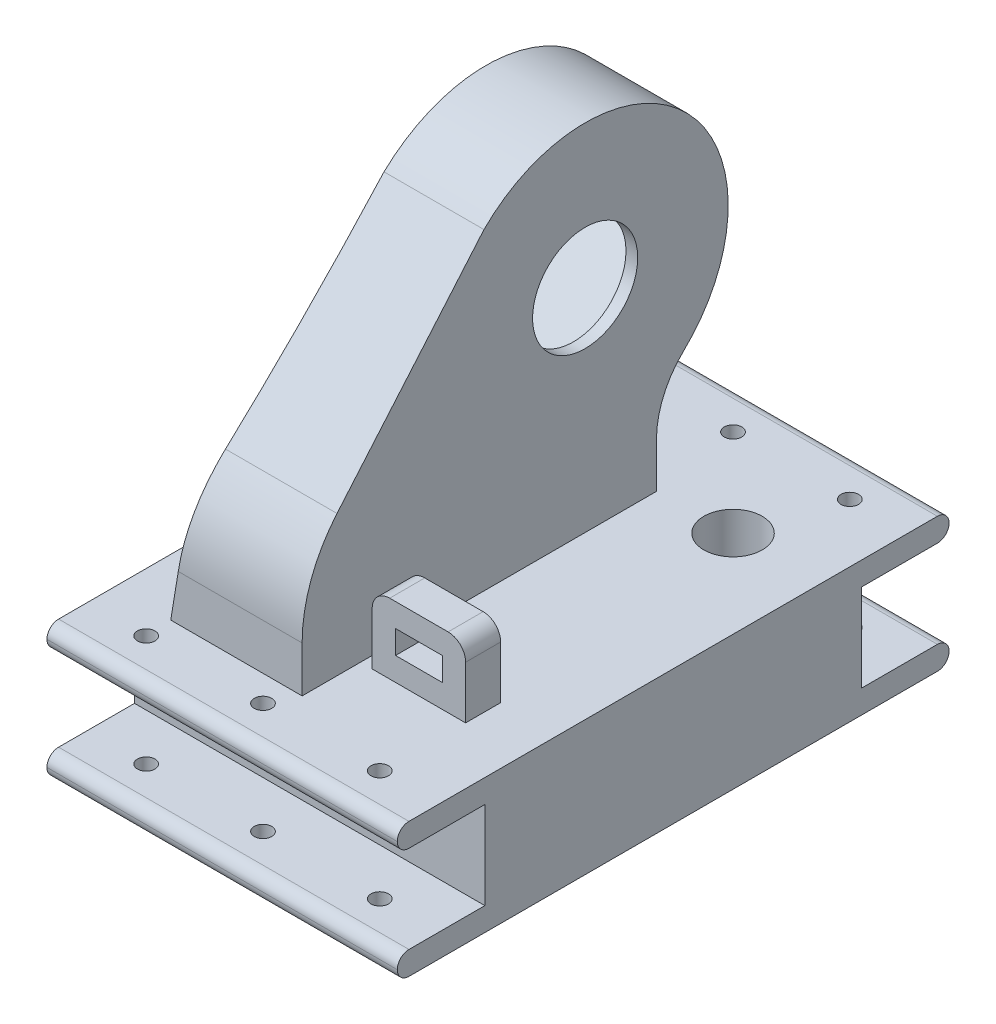
SolidWorks part; units mm, degrees
ref_plane "Front Plane" through (0, 0, 0) normal (0, 0, 1) x (1, 0, 0)
ref_plane "Top Plane" through (0, 0, 0) normal (0, 1, 0) x (1, 0, 0)
ref_plane "Right Plane" through (0, 0, 0) normal (1, 0, 0) x (0, 0, -1)
sketch "Sketch2" plane through (0, 0, 0) normal (0, 1, 0) x (1, 0, 0)
  circle A0 centre (0, 0) radius 48.5
  dimension "D1" = 97
extrude "Boss-Extrude1" add sketch "Sketch2" along normal blind 4
ref_plane "Plane1" through (-4, 0, 0) normal (1, 0, 0) x (0, 0, -1)
sketch "Sketch7" plane through (-4, 0, 0) normal (1, 0, 0) x (0, 0, -1)
  line L0 (23.1299, 11.6445) -> (23.1299, 4)
  line L5 (48.5, 4) -> (-48.5, 4) construction
  line L6 (-27.2273, 29.5362) -> (-1.2843, 55.4793)
  line L7 (-43.5609, 4) -> (23.1299, 4)
  line L11 (-34.5496, 4) -> (-34.5496, 11.8586)
  arc A4 (28.7298, 24.692) -> (-1.2843, 55.4793) centre (13.9185, 40.2765) ccw
  arc A5 (28.7298, 24.692) -> (23.1299, 11.6445) centre (41.1299, 11.6445) ccw
  arc A6 (-27.2273, 29.5362) -> (-34.5496, 11.8586) centre (-9.5496, 11.8586) ccw
  dimension "D1" = 25
  dimension "D4" = 43
  dimension "D3" = 18
  dimension "D5" = 45
extrude "Boss-Extrude2" add sketch "Sketch7" against normal blind 14 contours A5 A4 L6 L7 L0 | A4 | A4 | A4 | L6 A6 L7 region at (-4, 29.3392, -2.7362)
ref_plane "Plane2" through (-6, 0, 0) normal (1, 0, 0) x (0, 0, -1)
sketch "Sketch8" plane through (-6, 0, 0) normal (1, 0, 0) x (0, 0, -1)
  line L0 (-27.2273, 29.5362) -> (-1.2843, 55.4793) construction
  line L1 (-15.2496, 25.9576) -> (13.7417, 54.9489)
  line L2 (-15.2496, 25.9576) -> (-0.4004, 11.1083)
  line L3 (-0.4004, 11.1083) -> (28.591, 40.0997)
  line L4 (13.7417, 54.9489) -> (28.591, 40.0997)
  line L5 (-15.2496, 25.9576) -> (28.591, 40.0997) construction
  line L6 (-0.4004, 11.1083) -> (13.7417, 54.9489) construction
  point P0 (6.6707, 33.0286)
  point P11 (13.9185, 40.2765)
  dimension "D1" = 41
  dimension "D2" = 21
  dimension "D3" = 90
  dimension "D4" = 20.5
  dimension "D5" = 90
  dimension "D6" = 10.25
  dimension "D7" = 10.5
extrude "Cut-Extrude5" cut sketch "Sketch8" against normal up to next
sketch "Sketch9" plane through (-18, 0, 0) normal (-1, 0, 0) x (0, 0, 1)
  line L0 (-13.7417, 54.9489) -> (-28.591, 40.0997) construction
  line L3 (-21.1664, 47.5243) -> (-22.536, 48.894) construction
  circle A0 centre (-20.1057, 53.5347) radius 1.3
  circle A1 centre (-27.1768, 46.4637) radius 1.3
  circle A2 centre (6.7644, 12.5225) radius 1.3
  circle A3 centre (13.8354, 19.5936) radius 1.3
  dimension "D1" = 2.6
  dimension "D5" = 5
  dimension "D6" = 90
  dimension "D2" = 3.5
  dimension "D3" = 2
  dimension "D4" = 2
extrude "Cut-Extrude6" cut sketch "Sketch9" against normal blind 7.5
sketch "Sketch11" plane through (-4, 0, 0) normal (1, 0, 0) x (0, 0, -1)
  circle A0 centre (13.9185, 40.2765) radius 9
  dimension "D1" = 18
extrude "Cut-Extrude9" cut sketch "Sketch11" against normal up to next
sketch "Sketch17" plane through (-18, 0, 0) normal (-1, 0, 0) x (0, 0, 1)
  line L0 (29.3486, 31.6576) -> (3.4056, 57.6006)
  line L1 (-26.1299, 11.6445) -> (-26.1299, 1)
  line L2 (-26.1299, 1) -> (37.5496, 1)
  line L3 (37.5496, 1) -> (37.5496, 11.8586)
  line L4 (27.2273, 29.5362) -> (1.2843, 55.4793)
  line L5 (-23.1299, 11.6445) -> (-23.1299, 4)
  line L6 (-23.1299, 4) -> (34.5496, 4)
  line L7 (34.5496, 4) -> (34.5496, 11.8586)
  line L9 (-23.1299, 11.6445) -> (-23.1299, 4)
  line L10 (-23.1299, 4) -> (34.5496, 4)
  line L11 (34.5496, 4) -> (34.5496, 11.8586)
  line L12 (-26.1299, 4) -> (37.5496, 4)
  line L13 (48.5, 4) -> (-48.5, 4) construction
  line L14 (3.4056, 57.6006) -> (28.5745, 28.0776)
  line L15 (1.2843, 55.4793) -> (26.295, 26.1272)
  line L16 (31.5496, 11.8586) -> (31.5496, 4)
  line L18 (27.2273, 29.5362) -> (1.2843, 55.4793) construction
  arc A0 (3.4056, 57.6006) -> (-30.7965, 22.5174) centre (-13.9185, 40.2765) ccw
  arc A1 (-26.1299, 11.6445) -> (-30.7965, 22.5174) centre (-41.1299, 11.6445) ccw
  arc A2 (37.5496, 11.8586) -> (29.3486, 31.6576) centre (9.5496, 11.8586) ccw
  arc A3 (1.2843, 55.4793) -> (-28.7298, 24.692) centre (-13.9185, 40.2765) ccw
  arc A4 (-23.1299, 11.6445) -> (-28.7298, 24.692) centre (-41.1299, 11.6445) ccw
  arc A5 (34.5496, 11.8586) -> (27.2273, 29.5362) centre (9.5496, 11.8586) ccw
  arc A6 (1.2843, 55.4793) -> (-28.7298, 24.692) centre (-13.9185, 40.2765) ccw
  arc A7 (-23.1299, 11.6445) -> (-28.7298, 24.692) centre (-41.1299, 11.6445) ccw
  arc A8 (34.5496, 11.8586) -> (27.2273, 29.5362) centre (9.5496, 11.8586) ccw
  arc A9 (31.5496, 11.8586) -> (25.106, 27.4149) centre (9.5496, 11.8586) ccw
  line M16 (27.2273, 29.5362) -> (1.2843, 55.4793)
  arc M17 (1.2843, 55.4793) -> (-28.7298, 24.692) centre (-13.9185, 40.2765) ccw
  arc M18 (-28.7298, 24.692) -> (-23.1299, 11.6445) centre (-41.1299, 11.6445) cw
  line M19 (-23.1299, 11.6445) -> (-23.1299, 4)
  line M21 (34.5496, 4) -> (34.5496, 11.8586)
  arc M22 (34.5496, 11.8586) -> (27.2273, 29.5362) centre (9.5496, 11.8586) ccw
  dimension "D1" = 0
  dimension "D2" = 3
  dimension "D3" = 3
extrude "Boss-Extrude7" add sketch "Sketch17" along normal blind 9 and the other way up to surface (14 mm away) contours A9 L16 L12 L15 M21 M22 M16 | A1 L1 L12 L14 A0 M19 M18 M17 M16 M22 region at (-18, 42.2523, 15.3017) region at (-18, 20.289, 32.4332) other way up to face at (-4, 40.2765, -22.9185)
sketch "Sketch25" plane through (-18, 0, 0) normal (-1, 0, 0) x (0, 0, 1)
  line L0 (-23.1299, 11.6445) -> (-23.1299, 4)
  line L1 (48.5, 4) -> (-48.5, 4) construction
  line L2 (-23.1299, 11.6445) -> (-23.1299, 4) construction
  line L3 (1.2843, 55.4793) -> (26.295, 26.1272) construction
  line L4 (31.5496, 4) -> (-23.1299, 4) construction
  line L5 (31.5496, 11.8586) -> (31.5496, 4) construction
  line L6 (31.5496, 4) -> (-23.1299, 4)
  line L7 (31.5496, 11.8586) -> (31.5496, 4)
  line L8 (1.2843, 55.4793) -> (26.295, 26.1272)
  arc A0 (-23.1299, 11.6445) -> (-28.7298, 24.692) centre (-41.1299, 11.6445) ccw construction
  arc A1 (1.2843, 55.4793) -> (-28.7298, 24.692) centre (-13.9185, 40.2765) ccw construction
  arc A2 (-23.1299, 11.6445) -> (-28.7298, 24.692) centre (-41.1299, 11.6445) ccw
  arc A3 (31.5496, 11.8586) -> (26.295, 26.1272) centre (9.5496, 11.8586) ccw construction
  arc A4 (31.5496, 11.8586) -> (26.295, 26.1272) centre (9.5496, 11.8586) ccw
  spline S0 degree 3 poles (-28.7298, 24.692) (-21.9549, 18.2532) (-19.0941, 12.798) (-15.1299, 4) knots 0 0 0 0 1 1 1 1
  spline S1 degree 2 poles (11.7517, 43.1949) (26.5513, 25.8264) (25.5496, 4) knots 0 0 0 1 1 1
  dimension "D2" = 8
  dimension "D1" = 6
extrude "Boss-Extrude10" add sketch "Sketch25" along normal up to surface (9 mm away) contours S0 L6 L0 A2 | A4 S1 A2 S0 L8 region at (-18, 9.918, -20.706) region at (-18, 17.2592, 26.6261) up to face at (-27, 22.2911, 0.3951)
sketch "Sketch26" plane through (0, 0, 0) normal (0, 0, 1) x (1, 0, 0)
  line L0 (-4, 64.7765) -> (-27, 64.7765) construction
  line L1 (-27, 4) -> (-4, 4) construction
  line L2 (-27, 4) -> (-27, 11.8586) construction
  line L3 (-26, 64.7765) -> (-27, 64.7765)
  line L4 (-27, 64.7765) -> (-27, 4)
  line L5 (-27, 4) -> (-23, 4)
  spline S0 degree 2 poles (-26, 64.7765) (-24.7724, 34.3751) (-23, 4) knots 0 0 0 1 1 1
  dimension "D1" = 1
  dimension "D2" = 4
  dimension "D3" = 2
extrude "Cut-Extrude15" [suppressed] cut sketch "Sketch26" against normal through all both and the other way through all contours L4 L5 S0 L3
sketch "Sketch27" plane through (0, 4, 0) normal (0, 1, 0) x (1, 0, 0)
  line L1 (-2, -18.5496) -> (14, -18.5496)
  line L2 (-2, -18.5496) -> (-2, -24.5496)
  line L3 (-2, -24.5496) -> (14, -24.5496)
  line L4 (14, -18.5496) -> (14, -24.5496)
  line L5 (-27, -34.5496) -> (-4, -34.5496) construction
  line L6 (-4, -34.5496) -> (-4, 26.1299) construction
  dimension "D1" = 10
  dimension "D2" = 6
  dimension "D3" = 16
  dimension "D4" = 2
extrude "Boss-Extrude11" add sketch "Sketch27" along normal blind 12
fillet "Fillet6" radius 3 2 edges at (14, 16, 21.5496) (-2, 16, 21.5496)
sketch "Sketch28" plane through (0, 0, 24.5496) normal (0, 0, 1) x (1, 0, 0)
  line L8 (10, 12) -> (2, 12)
  line L9 (2, 12) -> (2, 8)
  line L10 (2, 8) -> (10, 8)
  line L11 (10, 8) -> (10, 12)
  line L12 (10, 12) -> (2, 12)
  line L13 (2, 12) -> (2, 8)
  line L14 (2, 8) -> (10, 8)
  line L15 (10, 8) -> (10, 12)
  dimension "D1" = 4
extrude "Cut-Extrude16" cut sketch "Sketch28" against normal up to next
sketch "Sketch29" plane through (0, 0, 0) normal (0, 0, 1) x (1, 0, 0)
  line L0 (-4, 64.7765) -> (-27, 64.7765) construction
  line L1 (-27, 4) -> (-4, 4) construction
  line L2 (-21, 64.7765) -> (-27, 64.7765)
  line L3 (-27, 64.7765) -> (-27, 4)
  line L4 (-27, 4) -> (-26.5, 4)
  line L5 (48.5, 4) -> (-48.5, 4) construction
  spline S0 degree 2 poles (-21, 64.7765) (-21.2205, 34.1409) (-26.5, 4) knots 0 0 0 1 1 1
  dimension "D1" = 6
  dimension "D2" = 4
  dimension "D3" = 0.5
  dimension "D4" = 25
extrude "Cut-Extrude17" cut sketch "Sketch29" against normal through all both and the other way through all
sketch "Sketch30" plane through (0, 0, 0) normal (0, 1, 0) x (1, 0, 0)
  line L2 (-36.253, 32.2175) -> (-36.253, -32.2175)
  line L3 (-15.3704, -46) -> (15.3704, -46)
  line L4 (23.747, 42.2886) -> (23.747, -42.2886)
  arc A0 (-36.253, 32.2175) -> (-36.253, -32.2175) centre (0, 0) ccw
  arc A1 (23.747, -42.2886) -> (23.747, 42.2886) centre (0, 0) ccw
  circle A2 centre (0, 0) radius 48.5
  arc A3 (-15.3704, -46) -> (15.3704, -46) centre (0, 0) ccw
  dimension "D3" = 0
extrude "Cut-Extrude18" cut sketch "Sketch30" along normal up to surface (4 mm away) up to face at (-18.75, 4, 4.7098)
sketch "Sketch33" plane through (0, 0, 0) normal (0, -1, 0) x (1, 0, 0)
  line L0 (15.3704, 46) -> (-15.3704, 46) construction
  line L1 (0, -48.5) -> (23.747, -48.5)
  line L2 (-36.253, 32.2175) -> (-36.253, -32.2175) construction
  line L3 (23.747, -48.5) -> (23.747, -42.2886)
  line L4 (23.747, -42.2886) -> (23.747, 42.2886) construction
  line L5 (-36.253, -32.2175) -> (-36.253, -48.5)
  line L6 (-36.253, -48.5) -> (0, -48.5)
  line L13 (23.747, -42.2886) -> (23.747, 42.2886)
  line L14 (15.3704, 46) -> (-15.3704, 46)
  line L15 (-36.253, 32.2175) -> (-36.253, -32.2175)
  line L16 (-15.3704, 46) -> (-36.253, 46)
  line L17 (-36.253, 46) -> (-36.253, 32.2175)
  line L18 (15.3704, 46) -> (23.747, 46)
  line L19 (23.747, 46) -> (23.747, 42.2886)
  arc A0 (-36.253, -32.2175) -> (23.747, -42.2886) centre (0, 0) ccw construction
extrude "Boss-Extrude12" add sketch "Sketch33" against normal up to surface (4 mm away) up to face at (-18.75, 4, 4.7098)
sketch "Sketch35" plane through (23.747, 0, 0) normal (1, 0, 0) x (0, 0, -1)
  line L0 (48.5, -15) -> (48.5, -19)
  line L1 (-46, 4) -> (48.5, 4)
  line L5 (48.5, 0) -> (33.5, 0)
  line L6 (48.5, 0) -> (-46, 0) construction
  line L7 (33.5, 0) -> (33.5, -15)
  line L8 (33.5, -15) -> (48.5, -15)
  line L9 (48.5, -19) -> (-46, -19)
  line L11 (-46, 4) -> (-46, 0)
  line L12 (-46, 0) -> (-31, 0)
  line L13 (-31, 0) -> (-31, -15)
  line L14 (-31, -15) -> (-46, -15)
  line L15 (-46, -15) -> (-46, -19)
  line L16 (48.5, 4) -> (48.5, 0)
  dimension "D1" = 15
  dimension "D2" = 15
  dimension "D3" = 15
  dimension "D4" = 15
  dimension "D5" = 4
  dimension "D6" = 4
  dimension "D7" = 15
extrude "Boss-Extrude13" add sketch "Sketch35" against normal up to surface (60 mm away) up to face at (-36.253, 2, -1.25)
fillet "Fillet7" radius 2 8 edges at (-6.253, -19, -48.5) (-6.253, -15, -48.5) (-6.253, 0, -48.5) (-6.253, 4, -48.5) (-6.253, -19, 46) (-6.253, -15, 46) (-6.253, 0, 46) (-6.253, 4, 46)
sketch "Sketch34" plane through (0, 4, 0) normal (0, 1, 0) x (1, 0, 0)
  line L0 (23.747, 46.5) -> (23.747, -44) construction
  line L1 (23.747, 46.5) -> (-36.253, 46.5) construction
  circle A2 centre (8.747, 26.5) radius 5
  dimension "D1" = 15
  dimension "D2" = 20
extrude "Cut-Extrude19" cut sketch "Sketch34" against normal through all
sketch "Sketch36" plane through (0, 4, 0) normal (0, 1, 0) x (1, 0, 0)
  line L2 (-36.253, 41.5) -> (23.747, 41.5)
  line L3 (-36.253, 41.5) -> (23.747, 41.5) construction
  line L4 (-6.253, 53.3208) -> (-6.253, -52.7561) construction
  line L5 (23.747, -39) -> (-36.253, -39)
  line L6 (23.747, -39) -> (-36.253, -39) construction
  line L7 (-36.253, 1.25) -> (23.747, 1.25) construction
  line L8 (-36.253, -44) -> (-36.253, 46.5) construction
  line L9 (23.747, 46.5) -> (23.747, -44) construction
  circle A0 centre (-6.253, 41.5) radius 1.5
  circle A1 centre (13.747, 41.5) radius 1.5
  circle A2 centre (-26.253, 41.5) radius 1.5
  circle A3 centre (-26.253, -39) radius 1.5
  circle A4 centre (-6.253, -39) radius 1.5
  circle A5 centre (13.747, -39) radius 1.5
  dimension "D3" = 20
  dimension "D5" = 3
  dimension "D6" = 3
  dimension "D7" = 3
  dimension "D8" = 3
  dimension "D4" = 20
  dimension "D1" = 7
  dimension "D2" = 7
extrude "Cut-Extrude20" cut sketch "Sketch36" against normal through all
